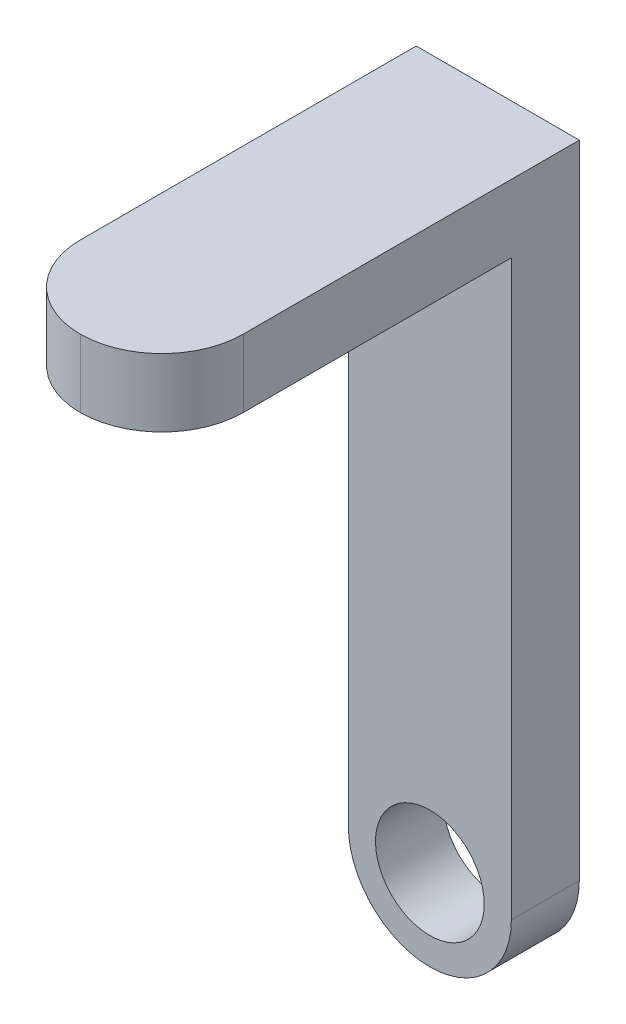
SolidWorks part; units mm, degrees
ref_plane "Front Plane" through (0, 0, 0) normal (0, 0, 1) x (1, 0, 0)
ref_plane "Top Plane" through (0, 0, 0) normal (0, 1, 0) x (1, 0, 0)
ref_plane "Right Plane" through (0, 0, 0) normal (1, 0, 0) x (0, 0, -1)
sketch "Sketch1" plane through (0, 0, 0) normal (0, 0, 1) x (1, 0, 0)
  line L0 (-2.6458, 3) -> (2.6458, 3)
  arc A0 (-2.6458, 3) -> (2.6458, 3) centre (0, 0) ccw
  circle A1 centre (0, 0) radius 6
  point P5 (0, -4)
  point P6 (0, 3)
  dimension "D1" = 8
  dimension "D3" = 12
  dimension "D2" = 7
extrude "Boss-Extrude1" add sketch "Sketch1" along normal blind 5
sketch "Sketch2" plane through (0, 0, 5) normal (0, 0, 1) x (1, 0, 0)
  line L0 (-6, 0) -> (-6, 47.2)
  line L1 (6, 0) -> (6, 47.2)
  line L2 (6, 47.2) -> (-6, 47.2)
  circle A0 centre (0, 0) radius 6 construction
  arc A1 (6, 0) -> (-6, 0) centre (0, 0) ccw
  dimension "D1" = 47.2
extrude "Boss-Extrude2" add sketch "Sketch2" against normal blind 5
sketch "Sketch3" plane through (0, 0, 5) normal (0, 0, 1) x (1, 0, 0)
  circle A0 centre (0, 0) radius 4
  dimension "D1" = 8
extrude "Cut-Extrude1" cut sketch "Sketch3" against normal blind 3
sketch "Sketch4" plane through (0, 0, 5) normal (0, 0, 1) x (1, 0, 0)
  line L0 (-6, 47.2) -> (-6, 42.2)
  line L1 (-6, 47.2) -> (-6, 0) construction
  line L2 (-6, 42.2) -> (6, 42.2)
  line L3 (6, 0) -> (6, 47.2) construction
  line L4 (6, 42.2) -> (6, 47.2)
  line L5 (6, 47.2) -> (-6, 47.2)
  dimension "D1" = 5
extrude "Boss-Extrude3" add sketch "Sketch4" along normal blind 25.73
fillet "Fillet1" radius 6 2 edges at (-6, 44.7, 30.73) (6, 44.7, 30.73)
